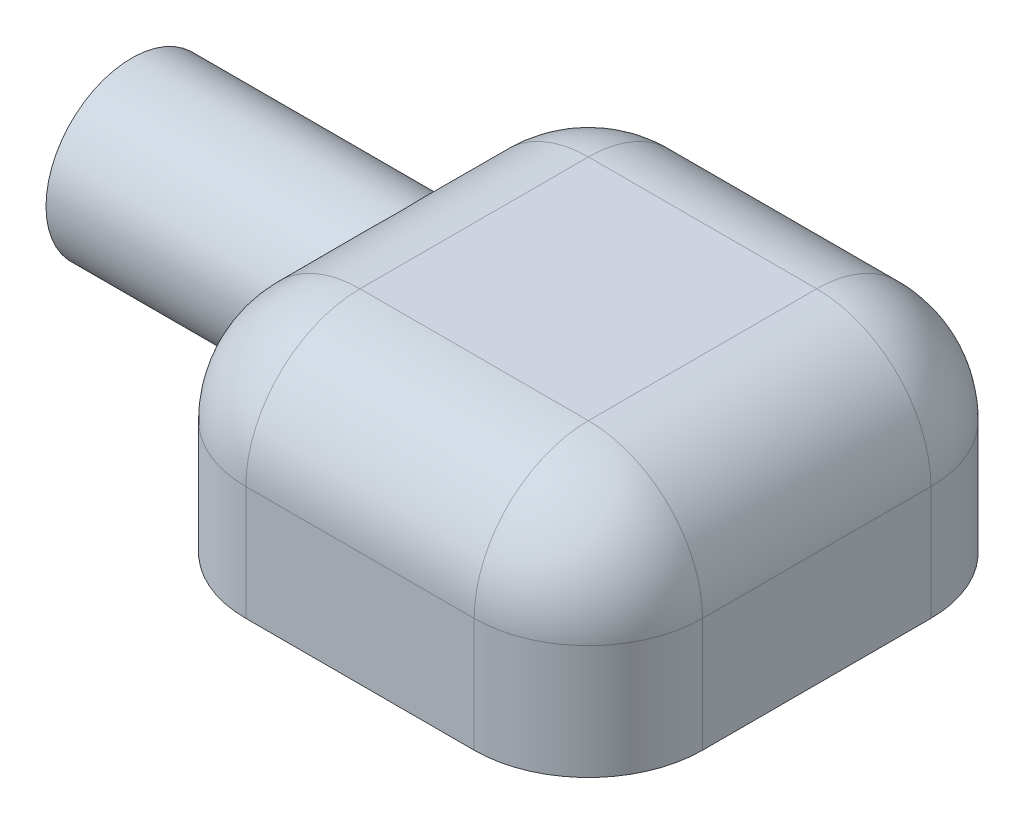
SolidWorks part; units mm, degrees
ref_plane "Front" through (0, 0, 0) normal (0, 0, 1) x (1, 0, 0)
ref_plane "Top" through (0, 0, 0) normal (0, 1, 0) x (1, 0, 0)
ref_plane "Right" through (0, 0, 0) normal (1, 0, 0) x (0, 0, -1)
sketch "Sketch1" plane through (0, 0, 0) normal (0, 1, 0) x (1, 0, 0)
  line L1 (20, -20) -> (-20, -20)
  line L2 (20, -20) -> (20, 20)
  line L3 (20, 20) -> (-20, 20)
  line L4 (-20, -20) -> (-20, 20)
  line L5 (20, -20) -> (-20, 20) construction
  line L6 (20, 20) -> (-20, -20) construction
  point P0 (0, 0)
  dimension "D1" = 40
  dimension "D2" = 40
extrude "Boss-Extrude1" add sketch "Sketch1" along normal blind 20
sketch "Sketch2" plane through (0, 0, 0) normal (0, -1, 0) x (1, 0, 0)
  line L1 (-20, -20) -> (-20, 20) construction
  circle A0 centre (0, 0) radius 5
  dimension "D1" = 10
  dimension "D2" = 20
extrude "Cut-Extrude1" cut sketch "Sketch2" against normal blind 10
sketch "Sketch3" plane through (-20, 0, 0) normal (-1, 0, 0) x (0, 0, 1)
  line L0 (0, 10) -> (0, 20) construction
  line L1 (-20, 20) -> (20, 20) construction
  line L2 (0, 10) -> (0, 0) construction
  line L3 (0, 10) -> (-20, 10) construction
  line L4 (-20, 20) -> (-20, 0) construction
  line L5 (0, 10) -> (20, 10) construction
  line L6 (20, 20) -> (20, 0) construction
  circle A0 centre (0, 10) radius 7.5
  dimension "D1" = 15
extrude "Boss-Extrude2" add sketch "Sketch3" along normal blind 20
fillet "Fillet1" radius 10 8 edges at (0, 20, 20) (20, 20, 0) (0, 20, -20) (-20, 20, 0) (-20, 10, -20) (20, 10, -20) (20, 10, 20) (-20, 10, 20)
